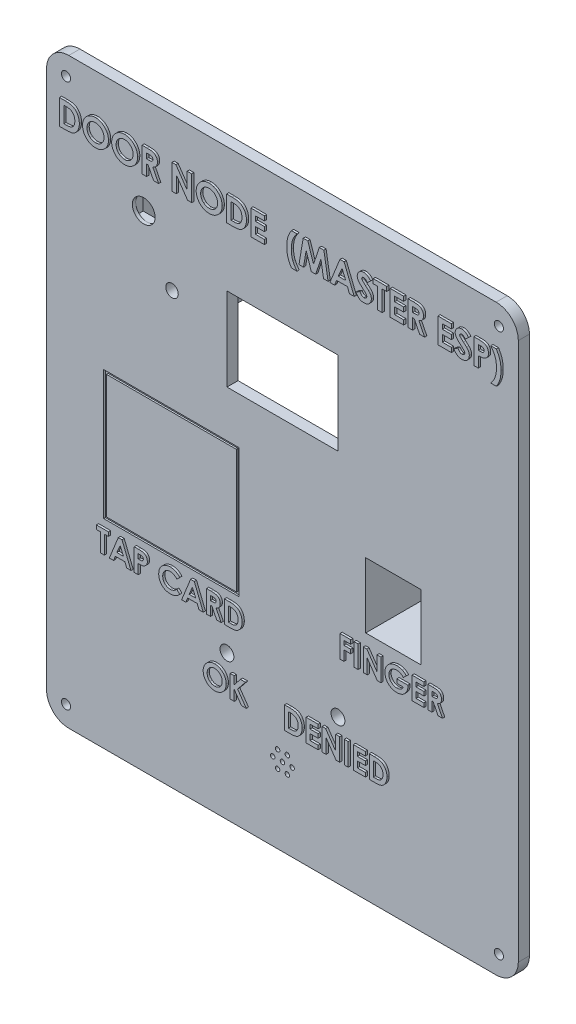
SolidWorks part; units mm, degrees
ref_plane "Front Plane" through (0, 0, 0) normal (0, 0, 1) x (1, 0, 0)
ref_plane "Top Plane" through (0, 0, 0) normal (0, 1, 0) x (1, 0, 0)
ref_plane "Right Plane" through (0, 0, 0) normal (1, 0, 0) x (0, 0, -1)
sketch "Sketch1" plane through (0, 0, 0) normal (0, 0, 1) x (1, 0, 0)
  line L0 (-77, 0) -> (77, 0)
  line L1 (85, 8) -> (85, 202)
  line L2 (77, 210) -> (-77, 210)
  line L3 (-85, 202) -> (-85, 8)
  arc A0 (-85, 8) -> (-77, 0) centre (-77, 8) ccw
  arc A1 (77, 0) -> (85, 8) centre (77, 8) ccw
  arc A2 (85, 202) -> (77, 210) centre (77, 202) ccw
  arc A3 (-77, 210) -> (-85, 202) centre (-77, 202) ccw
extrude "Panel" add sketch "Sketch1" along normal blind 4
ref_plane "P1_Front_4" through (0, 0, 4) normal (0, 0, 1) x (1, 0, 0)
sketch "Sketch2" plane through (0, 0, 0) normal (0, 0, 1) x (1, 0, 0)
  circle A0 centre (-78, 7) radius 1.65
  circle A1 centre (78, 7) radius 1.65
  circle A2 centre (-78, 203) radius 1.65
  circle A3 centre (78, 203) radius 1.65
extrude "Screw holes" cut sketch "Sketch2" along normal through all
ref_plane "P2_Front_-3" through (0, 0, -3) normal (0, 0, 1) x (1, 0, 0)
sketch "Sketch3" plane through (0, 0, -3) normal (0, 0, 1) x (1, 0, 0)
  line L1 (-15, 3.3) -> (15, 3.3)
  line L2 (-15, 3.3) -> (-15, 5.3)
  line L3 (-15, 5.3) -> (15, 5.3)
  line L4 (15, 3.3) -> (15, 5.3)
  line L6 (-15, 204.7) -> (15, 204.7)
  line L7 (-15, 204.7) -> (-15, 206.7)
  line L8 (-15, 206.7) -> (15, 206.7)
  line L9 (15, 204.7) -> (15, 206.7)
  line L11 (-81.7, 90) -> (-79.7, 90)
  line L12 (-81.7, 90) -> (-81.7, 120)
  line L13 (-81.7, 120) -> (-79.7, 120)
  line L14 (-79.7, 90) -> (-79.7, 120)
  line L16 (79.7, 90) -> (81.7, 90)
  line L17 (79.7, 90) -> (79.7, 120)
  line L18 (79.7, 120) -> (81.7, 120)
  line L19 (81.7, 90) -> (81.7, 120)
extrude "Locating tabs" add sketch "Sketch3" along normal blind 3
sketch "Sketch4" plane through (0, 0, 0) normal (0, 0, 1) x (1, 0, 0)
  line L1 (-20, 135) -> (20, 135)
  line L2 (-20, 135) -> (-20, 165)
  line L3 (-20, 165) -> (20, 165)
  line L4 (20, 135) -> (20, 165)
  line L5 (-20, 135) -> (20, 165) construction
  line L6 (-20, 165) -> (20, 135) construction
  point P0 (0, 150)
extrude "TFT window" cut sketch "Sketch4" along normal through all
ref_plane "P3_Front_-2.4" through (0, 0, -2.4) normal (0, 0, 1) x (1, 0, 0)
sketch "Sketch5" plane through (0, 0, -2.4) normal (0, 0, 1) x (1, 0, 0)
  circle A0 centre (-26, 135.75) radius 2.1
  circle A1 centre (-26, 164.25) radius 2.1
  circle A2 centre (26, 135.75) radius 2.1
  circle A3 centre (26, 164.25) radius 2.1
extrude "TFT bosses" add sketch "Sketch5" along normal blind 2.4
ref_plane "P4_Front_-2.4" through (0, 0, -2.4) normal (0, 0, 1) x (1, 0, 0)
sketch "Sketch6" plane through (0, 0, -2.4) normal (0, 0, 1) x (1, 0, 0)
  circle A0 centre (-26, 135.75) radius 1.1
  circle A1 centre (-26, 164.25) radius 1.1
  circle A2 centre (26, 135.75) radius 1.1
  circle A3 centre (26, 164.25) radius 1.1
extrude "TFT pilot holes" cut sketch "Sketch6" along normal blind 4
sketch "Sketch7" plane through (0, 0, 0) normal (0, 0, 1) x (1, 0, 0)
  line L1 (-61.425, 74.74) -> (-18.575, 74.74)
  line L2 (-61.425, 74.74) -> (-61.425, 115.26)
  line L3 (-61.425, 115.26) -> (-18.575, 115.26)
  line L4 (-18.575, 74.74) -> (-18.575, 115.26)
  line L5 (-61.425, 74.74) -> (-18.575, 115.26) construction
  line L6 (-61.425, 115.26) -> (-18.575, 74.74) construction
  circle A0 centre (-53.9, 82.4) radius 3
  circle A1 centre (-53.9, 107.6) radius 3
  circle A2 centre (-26.1, 82.4) radius 3
  circle A3 centre (-26.1, 107.6) radius 3
  point P0 (-40, 95)
extrude "NFC pocket" cut sketch "Sketch7" along normal blind 2.5
sketch "Sketch8" plane through (0, 0, 0) normal (0, 0, 1) x (1, 0, 0)
  circle A0 centre (-53.9, 82.4) radius 1.1
  circle A1 centre (-53.9, 107.6) radius 1.1
  circle A2 centre (-26.1, 82.4) radius 1.1
  circle A3 centre (-26.1, 107.6) radius 1.1
extrude "NFC pilot holes" cut sketch "Sketch8" along normal blind 3
sketch "Sketch9" plane through (0, 0, 4) normal (0, 0, 1) x (1, 0, 0)
  line L1 (-64.425, 71.74) -> (-15.575, 71.74)
  line L2 (-64.425, 71.74) -> (-64.425, 118.26)
  line L3 (-64.425, 118.26) -> (-15.575, 118.26)
  line L4 (-15.575, 71.74) -> (-15.575, 118.26)
  line L5 (-64.425, 71.74) -> (-15.575, 118.26) construction
  line L6 (-64.425, 118.26) -> (-15.575, 71.74) construction
  point P0 (-40, 95)
extrude "NFC tap outline recess" cut sketch "Sketch9" against normal blind 0.6
ref_plane "P5_Front_3.4" through (0, 0, 3.4) normal (0, 0, 1) x (1, 0, 0)
sketch "Sketch10" plane through (0, 0, 3.4) normal (0, 0, 1) x (1, 0, 0)
  line L1 (-63.425, 72.74) -> (-16.575, 72.74)
  line L2 (-63.425, 72.74) -> (-63.425, 117.26)
  line L3 (-63.425, 117.26) -> (-16.575, 117.26)
  line L4 (-16.575, 72.74) -> (-16.575, 117.26)
  line L5 (-63.425, 72.74) -> (-16.575, 117.26) construction
  line L6 (-63.425, 117.26) -> (-16.575, 72.74) construction
  point P0 (-40, 95)
extrude "NFC tap outline fill" add sketch "Sketch10" along normal blind 0.6
sketch "Sketch11" plane through (0, 0, 0) normal (0, 0, 1) x (1, 0, 0)
  line L1 (30, 83.25) -> (50, 83.25)
  line L2 (30, 83.25) -> (30, 106.75)
  line L3 (30, 106.75) -> (50, 106.75)
  line L4 (50, 83.25) -> (50, 106.75)
  line L5 (30, 83.25) -> (50, 106.75) construction
  line L6 (30, 106.75) -> (50, 83.25) construction
  point P0 (40, 95)
extrude "Fingerprint opening" cut sketch "Sketch11" along normal through all
ref_plane "P6_Front_-27.1" through (0, 0, -27.1) normal (0, 0, 1) x (1, 0, 0)
sketch "Sketch12" plane through (0, 0, -27.1) normal (0, 0, 1) x (1, 0, 0)
  line L1 (27.5, 80.75) -> (52.5, 80.75)
  line L2 (27.5, 80.75) -> (27.5, 109.25)
  line L3 (27.5, 109.25) -> (52.5, 109.25)
  line L4 (52.5, 80.75) -> (52.5, 109.25)
  line L5 (27.5, 80.75) -> (52.5, 109.25) construction
  line L6 (27.5, 109.25) -> (52.5, 80.75) construction
  line L7 (30, 83.25) -> (50, 83.25)
  line L8 (30, 83.25) -> (30, 106.75)
  line L9 (30, 106.75) -> (50, 106.75)
  line L10 (50, 83.25) -> (50, 106.75)
  line L11 (30, 83.25) -> (50, 106.75) construction
  line L12 (30, 106.75) -> (50, 83.25) construction
  point P0 (40, 95)
  point P5 (40, 95)
extrude "Fingerprint sleeve" add sketch "Sketch12" along normal blind 27.1
ref_plane "P7_Front_-29.1" through (0, 0, -29.1) normal (0, 0, 1) x (1, 0, 0)
sketch "Sketch13" plane through (0, 0, -29.1) normal (0, 0, 1) x (1, 0, 0)
  line L1 (27.5, 80.75) -> (33, 80.75)
  line L2 (27.5, 80.75) -> (27.5, 109.25)
  line L3 (27.5, 109.25) -> (33, 109.25)
  line L4 (33, 80.75) -> (33, 109.25)
  line L6 (47, 80.75) -> (52.5, 80.75)
  line L7 (47, 80.75) -> (47, 109.25)
  line L8 (47, 109.25) -> (52.5, 109.25)
  line L9 (52.5, 80.75) -> (52.5, 109.25)
extrude "Fingerprint back stop" add sketch "Sketch13" along normal blind 2
ref_plane "P8_Top_110.25" through (0, 110.25, 0) normal (0, 1, 0) x (1, 0, 0)
sketch "Sketch14" plane through (0, 110.25, 0) normal (0, 1, 0) x (1, 0, 0)
  circle A0 centre (40, 13.55) radius 1.1
extrude "Fingerprint clamp screw pilot" cut sketch "Sketch14" against normal through all
sketch "Sketch15" plane through (0, 0, 0) normal (0, 0, 1) x (1, 0, 0)
  circle A0 centre (-20, 52) radius 2.5
  circle A1 centre (20, 52) radius 2.5
extrude "LED holes" cut sketch "Sketch15" along normal through all
sketch "Sketch16" plane through (0, 0, 0) normal (0, 0, 1) x (1, 0, 0)
  circle A0 centre (0, 28) radius 0.8
  circle A1 centre (3.5, 28) radius 0.8
  circle A2 centre (1.75, 31.0311) radius 0.8
  circle A3 centre (-1.75, 31.0311) radius 0.8
  circle A4 centre (-3.5, 28) radius 0.8
  circle A5 centre (-1.75, 24.9689) radius 0.8
  circle A6 centre (1.75, 24.9689) radius 0.8
extrude "Buzzer sound holes" cut sketch "Sketch16" along normal through all
ref_plane "P9_Front_-7" through (0, 0, -7) normal (0, 0, 1) x (1, 0, 0)
sketch "Sketch17" plane through (0, 0, -7) normal (0, 0, 1) x (1, 0, 0)
  circle A0 centre (0, 28) radius 7.7
  circle A1 centre (0, 28) radius 6.1
extrude "Buzzer cradle" add sketch "Sketch17" along normal blind 7
sketch "Sketch18" plane through (0, 0, 0) normal (0, 0, 1) x (1, 0, 0)
  line L1 (-54.17, 170.83) -> (-45.83, 170.83)
  line L2 (-54.17, 170.83) -> (-54.17, 179.17)
  line L3 (-54.17, 179.17) -> (-45.83, 179.17)
  line L4 (-45.83, 170.83) -> (-45.83, 179.17)
  line L5 (-54.17, 170.83) -> (-45.83, 179.17) construction
  line L6 (-54.17, 179.17) -> (-45.83, 170.83) construction
  point P0 (-50, 175)
extrude "Camera block recess" cut sketch "Sketch18" along normal blind 2.8
sketch "Sketch19" plane through (0, 0, 0) normal (0, 0, 1) x (1, 0, 0)
  circle A0 centre (-50, 175) radius 4.095
  circle A1 centre (-39.8, 155.21) radius 2.25
extrude "Camera lens + flash holes" cut sketch "Sketch19" along normal through all
ref_plane "P10_Front_-17.3" through (0, 0, -17.3) normal (0, 0, 1) x (1, 0, 0)
sketch "Sketch20" plane through (0, 0, -17.3) normal (0, 0, 1) x (1, 0, 0)
  line L1 (-66.91, 143.91) -> (-64.91, 143.91)
  line L2 (-66.91, 143.91) -> (-66.91, 184.42)
  line L3 (-66.91, 184.42) -> (-64.91, 184.42)
  line L4 (-64.91, 143.91) -> (-64.91, 184.42)
  line L6 (-37.35, 143.91) -> (-35.35, 143.91)
  line L7 (-37.35, 143.91) -> (-37.35, 184.42)
  line L8 (-37.35, 184.42) -> (-35.35, 184.42)
  line L9 (-35.35, 143.91) -> (-35.35, 184.42)
extrude "Camera holder sides" add sketch "Sketch20" along normal blind 17.3
ref_plane "P11_Front_-17.3" through (0, 0, -17.3) normal (0, 0, 1) x (1, 0, 0)
sketch "Sketch21" plane through (0, 0, -17.3) normal (0, 0, 1) x (1, 0, 0)
  line L1 (-66.91, 184.42) -> (-35.35, 184.42)
  line L2 (-66.91, 184.42) -> (-66.91, 186.42)
  line L3 (-66.91, 186.42) -> (-35.35, 186.42)
  line L4 (-35.35, 184.42) -> (-35.35, 186.42)
extrude "Camera holder top" add sketch "Sketch21" along normal blind 17.3
ref_plane "P12_Right_-67.91" through (-67.91, 0, 0) normal (1, 0, 0) x (0, 0, -1)
sketch "Sketch22" plane through (-67.91, 0, 0) normal (1, 0, 0) x (0, 0, -1)
  line L1 (-16.05, 152.165) -> (-10.55, 152.165)
  line L2 (-16.05, 152.165) -> (-16.05, 156.165)
  line L3 (-16.05, 156.165) -> (-10.55, 156.165)
  line L4 (-10.55, 152.165) -> (-10.55, 156.165)
  line L5 (-16.05, 152.165) -> (-10.55, 156.165) construction
  line L6 (-16.05, 156.165) -> (-10.55, 152.165) construction
  line L7 (10.55, 152.165) -> (16.05, 152.165)
  line L8 (10.55, 152.165) -> (10.55, 156.165)
  line L9 (10.55, 156.165) -> (16.05, 156.165)
  line L10 (16.05, 152.165) -> (16.05, 156.165)
  line L11 (10.55, 152.165) -> (16.05, 156.165) construction
  line L12 (10.55, 156.165) -> (16.05, 152.165) construction
  line L13 (-16.05, 172.165) -> (-10.55, 172.165)
  line L14 (-16.05, 172.165) -> (-16.05, 176.165)
  line L15 (-16.05, 176.165) -> (-10.55, 176.165)
  line L16 (-10.55, 172.165) -> (-10.55, 176.165)
  line L17 (-16.05, 172.165) -> (-10.55, 176.165) construction
  line L18 (-16.05, 176.165) -> (-10.55, 172.165) construction
  line L19 (10.55, 172.165) -> (16.05, 172.165)
  line L20 (10.55, 172.165) -> (10.55, 176.165)
  line L21 (10.55, 176.165) -> (16.05, 176.165)
  line L22 (16.05, 172.165) -> (16.05, 176.165)
  line L23 (10.55, 172.165) -> (16.05, 176.165) construction
  line L24 (10.55, 176.165) -> (16.05, 172.165) construction
  point P0 (-13.3, 154.165)
  point P5 (13.3, 154.165)
  point P10 (-13.3, 174.165)
  point P15 (13.3, 174.165)
extrude "Camera tie slots" cut sketch "Sketch22" along normal through all
sketch "Sketch23" plane through (0, 0, 4) normal (0, 0, 1) x (1, 0, 0)
  text T0 "DOOR NODE  (MASTER ESP)" font "Century Gothic" height 9
  text T1 "TAP CARD" font "Century Gothic" height 8
  text T2 "FINGER" font "Century Gothic" height 8
  text T3 "OK" font "Century Gothic" height 8
  text T4 "DENIED" font "Century Gothic" height 8
extrude "Labels (raised)" add sketch "Sketch23" along normal blind 0.8
